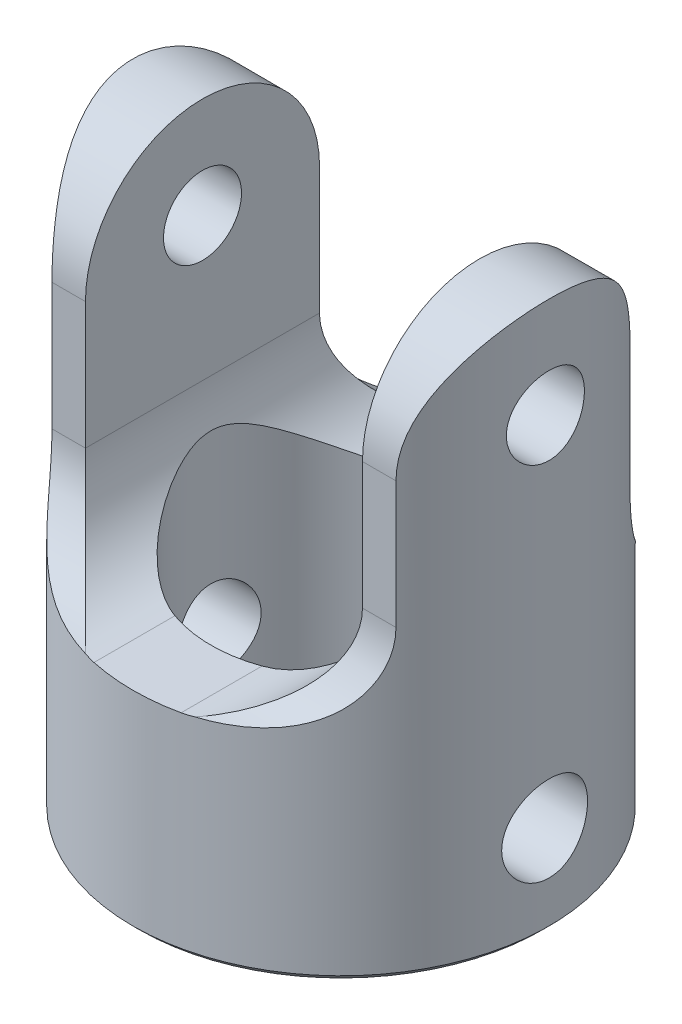
SolidWorks part; units mm, degrees
material "AISI 1045 Steel, cold drawn"
ref_plane "Front Plane" through (0, 0, 0) normal (0, 0, 1) x (1, 0, 0)
ref_plane "Top Plane" through (0, 0, 0) normal (0, 1, 0) x (1, 0, 0)
ref_plane "Right Plane" through (0, 0, 0) normal (1, 0, 0) x (0, 0, -1)
sketch "Sketch1" plane through (0, 0, 0) normal (0, 1, 0) x (1, 0, 0)
  circle A0 centre (0, 0) radius 8
  circle A1 centre (0, 0) radius 5
  dimension "D1" = 16
  dimension "D2" = 10
extrude "Boss-Extrude2" add sketch "Sketch1" along normal mid plane 25
sketch "Sketch3" plane through (0, 0, 0) normal (0, 0, 1) x (1, 0, 0)
  line L1 (-5.325, 13.5) -> (5.325, 13.5)
  line L2 (-5.325, 13.5) -> (-5.325, -4.4)
  line L3 (-5.325, -4.4) -> (5.325, -4.4)
  line L4 (5.325, 13.5) -> (5.325, -4.4)
  line L5 (-5.325, 13.5) -> (5.325, -4.4) construction
  line L6 (-5.325, -4.4) -> (5.325, 13.5) construction
  line L7 (-8, -12.5) -> (8, -12.5) construction
  line L8 (8, 12.5) -> (-8, 12.5) construction
  point P0 (0, 4.55)
  dimension "D1" = 10.65
  dimension "D2" = 8.1
  dimension "D3" = 1
extrude "Cut-Extrude1" cut sketch "Sketch3" against normal through all both and the other way through all
sketch "Sketch4" plane through (0, 0, 0) normal (1, 0, 0) x (0, 0, -1)
  line L0 (-4.5, -4.4) -> (-4.5, 4.13)
  line L1 (4.5, -4.4) -> (4.5, 4.13)
  line L2 (-5, -12.5) -> (5, -12.5) construction
  line L3 (4.5, -4.4) -> (5.9703, -4.4)
  line L5 (-5.9703, -4.4) -> (5.9703, -4.4)
  line L7 (5.9703, -4.4) -> (5.9703, 12.5)
  line L8 (5.9703, 12.5) -> (-5.9703, 12.5)
  line L9 (-5.9703, 12.5) -> (-5.9703, -4.4)
  line L10 (-5.9703, -4.4) -> (-4.5, -4.4)
  line L12 (5.9703, -4.4) -> (5.9703, 12.5)
  line L13 (5.9703, 12.5) -> (-5.9703, 12.5)
  line L14 (-5.9703, 12.5) -> (-5.9703, -4.4)
  arc A0 (-4.5, 4.13) -> (4.5, 4.13) centre (0, 4.13) cw
  dimension "D4" = 16.63
  dimension "D2" = 4.5
  dimension "D3" = 4.5
  dimension "D1" = 0
extrude "Cut-Extrude3" cut sketch "Sketch4" against normal through all both and the other way through all
fillet "Fillet10" radius 3.65 4 edges at (-5.9697, -4.4, -4.5) (5.9697, -4.4, -4.5) (5.9697, -4.4, 4.5) (-5.9697, -4.4, 4.5)
fillet "Fillet11" radius 3.65 2 edges at (5.325, -4.4, 0) (-5.325, -4.4, 0)
ref_plane "Plane1" through (8, 0, 0) normal (1, 0, 0) x (0, 0, -1)
ref_plane "Plane2" through (-8, 0, 0) normal (-1, 0, 0) x (0, 0, 1)
sketch "Sketch5" plane through (8, 0, 0) normal (1, 0, 0) x (0, 0, -1)
  line L0 (-8, -12.5) -> (8, -12.5) construction
  point P0 (0, -9)
  dimension "D1" = 3.5
sketch "Sketch7" plane through (-8, 0, 0) normal (-1, 0, 0) x (0, 0, 1)
  point P0 (0, -9)
hole_wizard "Ø3.3 (3.3) Diameter Hole1" positions "Sketch8" profile "Sketch9" hole size "Ø3.3" standard "ANSI Metric" end condition up to next
sketch "Sketch8" plane through (-8, 0, 0) normal (-1, 0, 0) x (0, 0, 1)
  point P0 (0, -9)
sketch "Sketch9" plane through (-8, -9, 0) normal (0, 1, 0) x (0, 0, 1)
  line L0 (0, 0) -> (0, 3)
  line L1 (0, 3) -> (1.65, 3)
  line L2 (1.65, 3) -> (1.65, 0)
  line L5 (1.65, 0) -> (0, 0)
  line L11 (0, -6.35) -> (0, 107.95) construction
  dimension "Thru Hole Dia." = 3.3
  dimension "Thru Hole Depth" = 3
hole_wizard "Ø3.3 (3.3) Diameter Hole2" positions "Sketch10" profile "Sketch11" hole size "Ø3.3" standard "ANSI Metric" end condition up to next
sketch "Sketch10" plane through (8, 0, 0) normal (1, 0, 0) x (0, 0, -1)
  point P0 (0, -9)
sketch "Sketch11" plane through (8, -9, 0) normal (0, 1, 0) x (0, 0, -1)
  line L0 (0, 0) -> (0, 3)
  line L1 (0, 3) -> (1.65, 3)
  line L2 (1.65, 3) -> (1.65, 0)
  line L5 (1.65, 0) -> (0, 0)
  line L11 (0, -6.35) -> (0, 107.95) construction
  dimension "Thru Hole Dia." = 3.3
  dimension "Thru Hole Depth" = 3
sketch "Sketch12" plane through (0, 0, 0) normal (1, 0, 0) x (0, 0, -1)
  line L0 (-8, -12.5) -> (8, -12.5) construction
  circle A0 centre (0, 4.75) radius 1.5
  dimension "D1" = 3
  dimension "D2" = 17.25
extrude "Cut-Extrude4" cut sketch "Sketch12" against normal through all both and the other way through all
chamfer "Chamfer1" distance 0.25 angle 45 2 edges at (0, -12.5, 5) (0, -12.5, 8)
